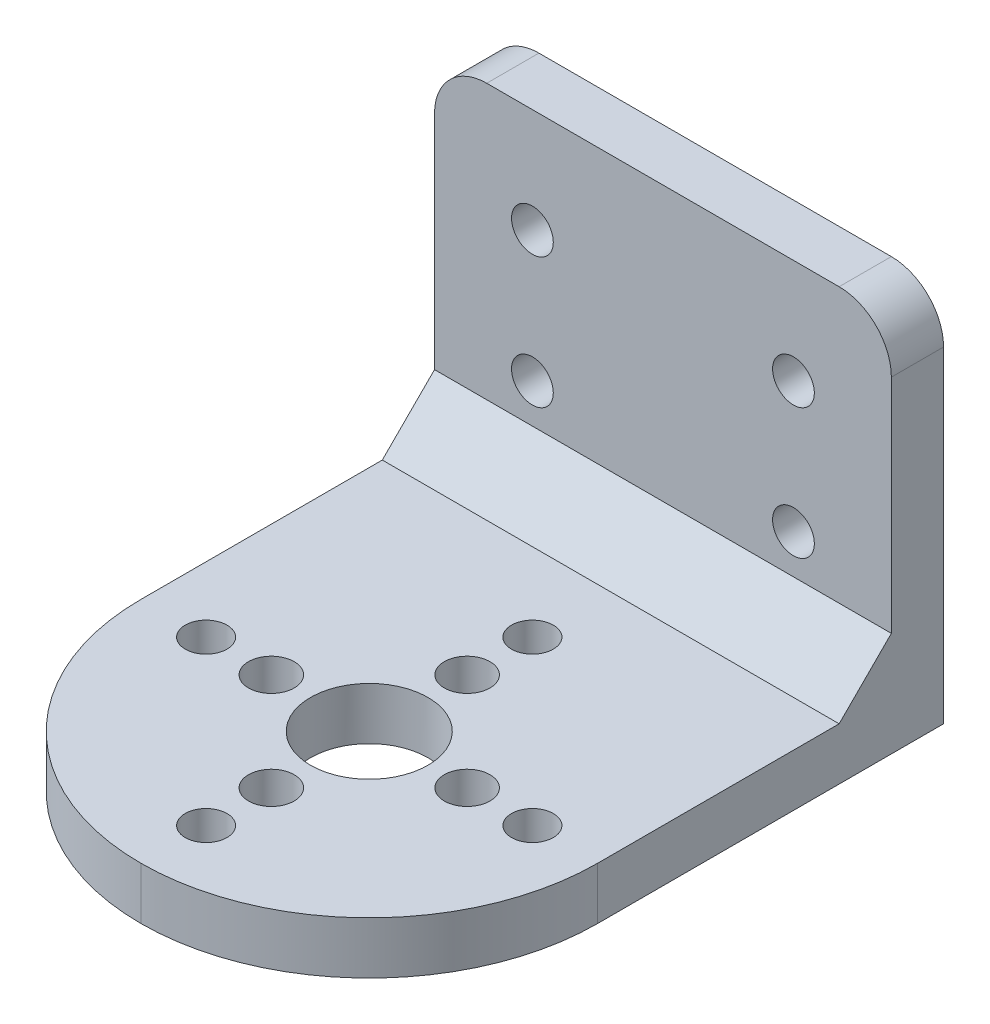
SolidWorks part; units mm, degrees
ref_plane "前视基准面" through (0, 0, 0) normal (0, 0, 1) x (1, 0, 0)
ref_plane "上视基准面" through (0, 0, 0) normal (0, 1, 0) x (1, 0, 0)
ref_plane "右视基准面" through (0, 0, 0) normal (1, 0, 0) x (0, 0, -1)
other "Configuration Table"
sketch "草图1" plane through (0, 0, 0) normal (0, 1, 0) x (1, 0, 0)
  line L1 (0, 0) -> (35, 0)
  line L2 (0, 0) -> (0, 44)
  line L3 (0, 44) -> (35, 44)
  line L4 (35, 0) -> (35, 44)
  dimension "D1" = 35
  dimension "D2" = 44
extrude "凸台-拉伸1" add sketch "草图1" along normal blind 4
sketch "草图2" plane through (0, 4, 0) normal (0, 1, 0) x (1, 0, 0)
  line L0 (35, 0) -> (35, 44) construction
  line L1 (0, 44) -> (35, 44)
  line L2 (0, 44) -> (0, 40)
  line L3 (0, 40) -> (35, 40)
  line L4 (35, 44) -> (35, 40)
  dimension "D1" = 4
extrude "凸台-拉伸2" add sketch "草图2" along normal blind 25
sketch "草图3" plane through (0, 4, 0) normal (0, 1, 0) x (1, 0, 0)
  line L0 (0, 0) -> (35, 0) construction
  line L1 (35, 0) -> (35, 40) construction
  line L2 (17.5, 17.5) -> (17.5, 25) construction
  line L3 (17.5, 17.5) -> (17.5, 10) construction
  line L4 (17.5, 17.5) -> (10, 17.5) construction
  line L5 (17.5, 17.5) -> (25, 17.5) construction
  line L6 (17.5, 17.5) -> (17.5, 30) construction
  line L7 (17.5, 17.5) -> (30, 17.5) construction
  line L8 (17.5, 17.5) -> (17.5, 5) construction
  line L9 (17.5, 17.5) -> (5, 17.5) construction
  circle A0 centre (17.5, 17.5) radius 4.5
  circle A1 centre (17.5, 25) radius 1.75
  circle A2 centre (25, 17.5) radius 1.75
  circle A3 centre (10, 17.5) radius 1.75
  circle A4 centre (17.5, 10) radius 1.75
  circle A5 centre (17.5, 30) radius 1.6
  circle A6 centre (30, 17.5) radius 1.6
  circle A7 centre (17.5, 5) radius 1.6
  circle A8 centre (5, 17.5) radius 1.6
  dimension "D1" = 9
  dimension "D2" = 3.5
  dimension "D3" = 3.5
  dimension "D4" = 3.5
  dimension "D5" = 3.5
  dimension "D6" = 3.2
  dimension "D7" = 3.2
  dimension "D8" = 3.2
  dimension "D9" = 3.2
  dimension "D10" = 17.5
  dimension "D11" = 17.5
  dimension "D12" = 15
  dimension "D13" = 15
  dimension "D15" = 25
  dimension "D16" = 25
extrude "切除-拉伸1" cut sketch "草图3" against normal blind 20
chamfer "倒角1" distance 4 angle 45 1 edges at (17.5, 4, -40)
sketch "草图5" plane through (0, 0, -40) normal (0, 0, 1) x (1, 0, 0)
  line L0 (0, 8) -> (35, 8) construction
  line L1 (7.5, 21) -> (27.5, 21) construction
  line L2 (7.5, 21) -> (7.5, 11) construction
  line L3 (7.5, 11) -> (27.5, 11) construction
  line L4 (27.5, 21) -> (27.5, 11) construction
  line L5 (0, 29) -> (0, 8) construction
  circle A0 centre (7.5, 21) radius 1.6
  circle A1 centre (27.5, 21) radius 1.6
  circle A2 centre (27.5, 11) radius 1.6
  circle A3 centre (7.5, 11) radius 1.6
  dimension "D5" = 3.2
  dimension "D6" = 3.2
  dimension "D7" = 3.2
  dimension "D8" = 3.2
  dimension "D1" = 20
  dimension "D2" = 10
  dimension "D3" = 3
  dimension "D4" = 7.5
extrude "切除-拉伸2" cut sketch "草图5" against normal blind 20
fillet "圆角1" radius 17.5 2 edges at (35, 2, 0) (0, 2, 0)
fillet "圆角2" radius 4 2 edges at (35, 29, -42) (0, 29, -42)
